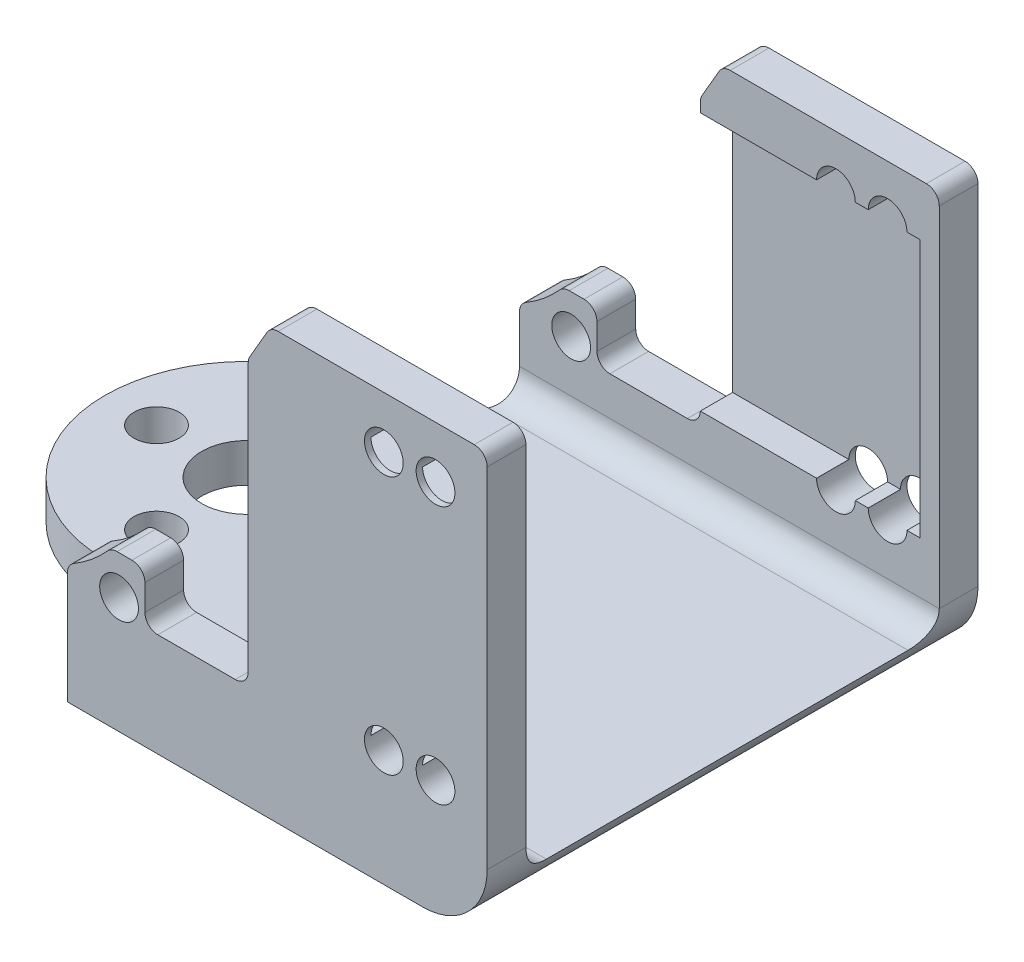
SolidWorks part; units mm, degrees
ref_plane "Спереди" through (0, 0, 0) normal (0, 0, 1) x (1, 0, 0)
ref_plane "Сверху" through (0, 0, 0) normal (0, 1, 0) x (1, 0, 0)
ref_plane "Справа" through (0, 0, 0) normal (1, 0, 0) x (0, 0, -1)
other "Configuration Table"
sketch "Эскиз1" plane through (0, 0, 0) normal (0, 0, 1) x (1, 0, 0)
  line L1 (10.25, -10) -> (-10.25, -10) construction
  line L2 (10.25, -10) -> (10.25, 10) construction
  line L3 (10.25, 10) -> (-10.25, 10) construction
  line L4 (-10.25, -10) -> (-10.25, 10) construction
  line L5 (10.25, -10) -> (-10.25, 10) construction
  line L6 (10.25, 10) -> (-10.25, -10) construction
  line L7 (10.25, 10) -> (14.25, 10) construction
  line L8 (10.25, 10) -> (10.25, -10) construction
  line L9 (10.25, -10) -> (14.25, -10) construction
  line L10 (14.25, 10) -> (14.25, -10) construction
  line L11 (-14.25, 14) -> (18.25, 14)
  line L12 (-14.25, 14) -> (-14.25, -19)
  line L13 (-14.25, -19) -> (18.25, -19)
  line L14 (18.25, 14) -> (18.25, -19)
  circle A0 centre (-10.25, 10) radius 1.5
  circle A1 centre (10.25, 10) radius 1.5
  circle A2 centre (14.25, 10) radius 1.5
  circle A3 centre (14.25, -10) radius 1.5
  circle A4 centre (-10.25, -10) radius 1.5
  circle A5 centre (10.25, -10) radius 1.5
  point P0 (0, 0)
  dimension "D4" = 3
  dimension "D1" = 4
  dimension "D2" = 20.5
  dimension "D3" = 20
  dimension "D5" = 4
  dimension "D6" = 4
  dimension "D7" = 9
  dimension "D8" = 4
extrude "Бобышка-Вытянуть1" add sketch "Эскиз1" against normal blind 38 contours L14 L11 L12 L13 A5 A4 A3 A2 A1 A0 region at (1.8868, -2.6029, 0)
sketch "Эскиз3" plane through (0, -19, 0) normal (0, -1, 0) x (1, 0, 0)
  line L0 (-19.35, -30) -> (-14.25, -30)
  line L1 (-14.25, -38) -> (-14.25, 0) construction
  line L2 (-14.25, -30) -> (-14.25, -8)
  line L3 (-14.25, -8) -> (-19.35, -8)
  line L4 (-19.35, -19) -> (-14.25, -19) construction
  circle A0 centre (-19.35, -19) radius 11
  line M4 (-14.25, 0) -> (-14.25, -38)
  dimension "D1" = 22
  dimension "D2" = 5.1
extrude "Бобышка-Вытянуть2" add sketch "Эскиз3" against normal blind 3 contours A0 L2 M4 | A0 L0 M4 | A0 L3 M4 | L2 A0 M4 region at (-15.51, -19, -29.6279) region at (-21.4204, -19, -19) region at (-15.51, -19, -8.3721) region at (-11.8256, -19, -19)
sketch "Эскиз4" plane through (-14.25, 0, 0) normal (-1, 0, 0) x (0, 0, 1)
  line L0 (-8, -16) -> (-30, -16) construction
  line L1 (-35, -16) -> (-3, -16)
  line L2 (-35, -16) -> (-35, 14)
  line L3 (-35, 14) -> (-3, 14)
  line L4 (-3, -16) -> (-3, 14)
  line L5 (-38, 14) -> (0, 14) construction
  point P5 (-19, -16)
  dimension "D1" = 32
extrude "Вырез-Вытянуть1" cut sketch "Эскиз4" against normal through all
sketch "Эскиз5" plane through (0, 0, 0) normal (0, 0, 1) x (1, 0, 0)
  line L0 (-10.25, -10) -> (-10.25, 10) construction
  line L1 (-10.25, 0) -> (-19.35, 0) construction
  line L2 (-9.8356, -5.5205) -> (1.4907, 14)
  line L3 (-14.25, 14) -> (18.25, 14) construction
  line L4 (1.4907, 14) -> (-14.25, 14)
  line L5 (-14.25, 14) -> (-14.25, 9.7463)
  line L6 (-14.25, 14) -> (-14.25, -19) construction
  line L7 (-8.25, -11) -> (-0.25, 11) construction
  line L8 (-8.25, -11) -> (-0.25, -11)
  line L9 (-8.25, -11) -> (-8.25, 11)
  line L10 (-8.25, 11) -> (-0.25, 11)
  line L11 (-0.25, -11) -> (-0.25, 11)
  line L12 (-10.8647, -7) -> (-8.25, -7)
  line L13 (-10.8647, -7) -> (-10.8647, 7)
  line L14 (-10.8647, 7) -> (-8.25, 7)
  line L15 (-8.25, -7) -> (-8.25, 7)
  line L16 (-8.25, 11) -> (-0.25, -11) construction
  line L17 (-4.25, 0) -> (-19.35, 0) construction
  circle A0 centre (-19.35, 0) radius 11
  point P24 (-8.25, 0)
  circle M8 centre (-10.25, 10) radius 1.5
  line M10 (18.25, 14) -> (-14.25, 14)
  line M11 (-14.25, 14) -> (-14.25, -19)
  dimension "D2" = 22
  dimension "D1" = 9.1
  dimension "D4" = 22
  dimension "D5" = 8
  dimension "D6" = 15.1
  dimension "D7" = 4
extrude "Вырез-Вытянуть2" cut sketch "Эскиз5" against normal through all contours A0 M11 | L13 A0 M11 | L13 A0 | A0 L12 L9 L2 | A0 L2 L9 L14 | L10 L9 L2 | L8 L11 L10 L2 L9 | A0 L14 L9 L10 L2 M10 M11 M8 region at (-7.6832, 11.7688, 0) region at (-3.6415, -2.9226, 0) region at (-5.5833, 6.4041, 0) region at (-9.0877, -5.6122, 0) region at (-8.9357, 4.0141, 0) region at (-9.8483, 0, 0) region at (-21.4204, 0, 0) region at (-12.6467, 0, 0)
fillet "Скругление2" radius 1 16 edges at (18.25, 14, -1.5) (18.25, 14, -36.5) (-0.25, -11, -36.5) (1.4907, 14, -1.5) (-0.25, 11, -1.5) (1.4907, 14, -36.5) (-0.25, 11, -36.5) (-0.25, -11, -1.5) (-8.25, -11, -36.5) (-8.25, -7, -36.5) (-10.8647, -7, -36.5) (-14.25, -9.7463, -36.5) (-14.25, -9.7463, -1.5) (-10.8647, -7, -1.5) (-8.25, -11, -1.5) (-8.25, -7, -1.5)
ref_plane "Плоскость1" through (0, 0, -19) normal (0, 0, 1) x (1, 0, 0)
sketch "Эскиз8" plane through (0, -19, 0) normal (0, -1, 0) x (1, 0, 0)
  circle A0 centre (-19.35, -19) radius 7 construction
  arc A1 (-19.35, -8) -> (-19.35, -30) centre (-19.35, -19) ccw construction
  circle A2 centre (-26.35, -19) radius 1.75
  circle A3 centre (-19.35, -12) radius 1.75
  circle A4 centre (-12.35, -19) radius 1.75
  circle A5 centre (-19.35, -26) radius 1.75
  dimension "D1" = 14
  dimension "D2" = 3.5
extrude "Вырез-Вытянуть4" cut sketch "Эскиз8" against normal through all
sketch "Эскиз10" plane through (0, 0, -3) normal (0, 0, -1) x (-1, 0, 0)
  line L0 (0.25, 0) -> (-18.25, 0) construction
  line L1 (0.25, -10) -> (0.25, 10.7309) construction
  line L2 (-18.25, 13) -> (-18.25, -19) construction
  line L4 (0.25, 10) -> (-16.75, 10)
  line L5 (0.25, 10) -> (0.25, -10)
  line L6 (0.25, -10) -> (-16.75, -10)
  line L7 (-16.75, 10) -> (-16.75, -10)
  point P11 (-16.75, 0)
  dimension "D1" = 20
  dimension "D2" = 17
extrude "Вырез-Вытянуть5" cut sketch "Эскиз10" against normal blind 2.5
mirror "Зеркальное отражение2" about plane through (0, 0, -19) normal (0, 0, 1) of "Вырез-Вытянуть5"
fillet "Скругление4" radius 5 1 edges at (18.25, -19, -19)
fillet "Скругление5" radius 5 2 edges at (-14.25, -17.5, -8) (-14.25, -17.5, -30)
sketch "Эскиз11" plane through (0, -16, 0) normal (0, 1, 0) x (1, 0, 0)
  circle A0 centre (-19.35, 19) radius 3.5
  arc A1 (-19.35, 30) -> (-19.35, 8) centre (-19.35, 19) ccw construction
  dimension "D1" = 7
extrude "Вырез-Вытянуть6" cut sketch "Эскиз11" against normal through all
fillet "Скругление6" radius 2 2 edges at (1.7913, -16, -3) (1.7913, -16, -35)
